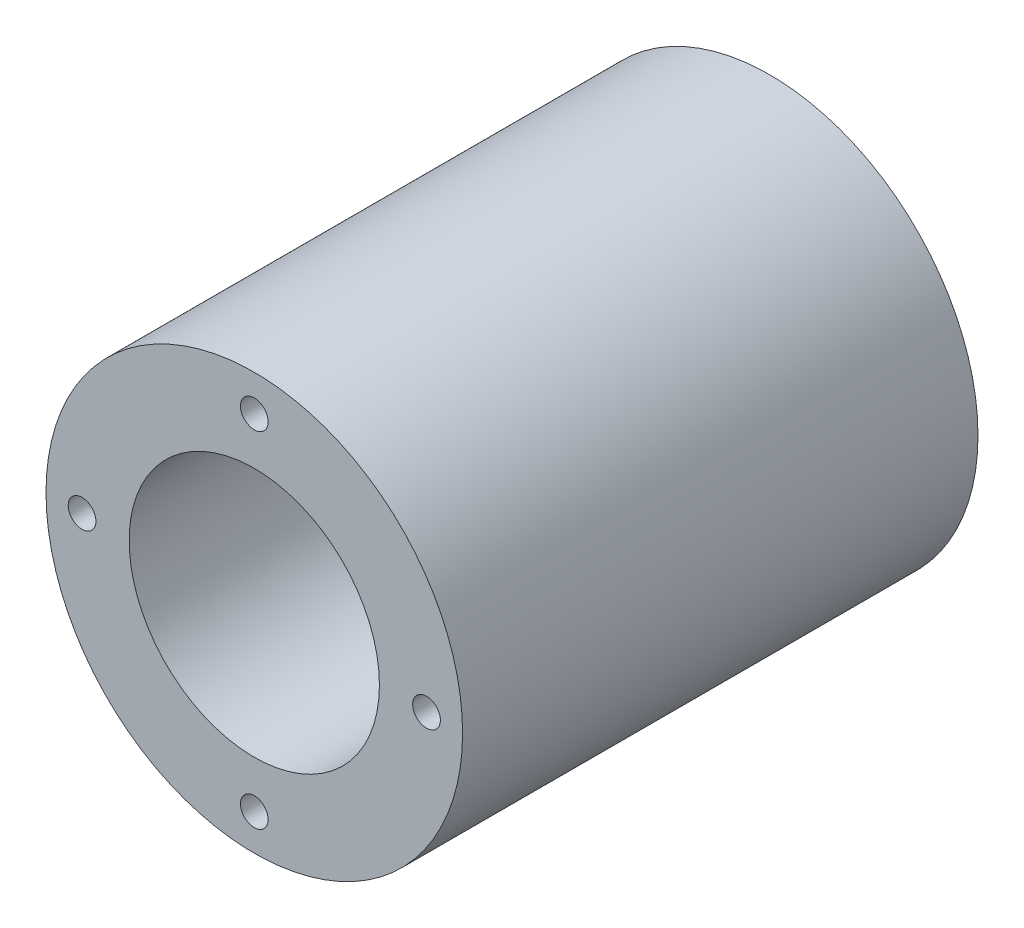
SolidWorks part; units mm, degrees
material "6061-T6 (SS)"
ref_plane "Front Plane" through (0, 0, 0) normal (0, 0, 1) x (1, 0, 0)
ref_plane "Top Plane" through (0, 0, 0) normal (0, 1, 0) x (1, 0, 0)
ref_plane "Right Plane" through (0, 0, 0) normal (1, 0, 0) x (0, 0, -1)
sketch "Sketch Spindle Skeleton" plane through (0, 0, 0) normal (1, 0, 0) x (0, 0, -1)
  line L0 (-95.847, -9.5) -> (-164, -9.5)
  line L5 (-1000, 0) -> (49000, 0)
  line L6 (0, -9.5) -> (0, 9.5)
  line L13 (0, 9.5) -> (-45.847, 9.5)
  line L26 (-45.847, 9.5) -> (-45.847, 14)
  line L27 (-45.847, 14) -> (-95.847, 14)
  line L32 (-95.847, 14) -> (-95.847, 9.5)
  line L34 (-180, 7) -> (-180, -7)
  line L36 (-95.847, -9.5) -> (-95.847, -14)
  line L37 (-95.847, -14) -> (-45.847, -14)
  line L38 (-45.847, -14) -> (-45.847, -9.5)
  line L39 (0, -9.5) -> (-45.847, -9.5)
  line L40 (-25.305, 37.6491) -> (-16.305, 37.6491)
  line L41 (-111.341, 22.6187) -> (-95.847, 22.6187)
  line L42 (-111.341, 22.6187) -> (-111.341, -22.6187)
  line L43 (-111.341, -22.6187) -> (-95.847, -22.6187)
  line L44 (-95.847, 22.6187) -> (-95.847, -22.6187)
  line L45 (-111.341, 22.6187) -> (-95.847, -22.6187) construction
  line L46 (-111.341, -22.6187) -> (-95.847, 22.6187) construction
  line L47 (-30.353, 22.6187) -> (-45.847, 22.6187)
  line L48 (-30.353, 22.6187) -> (-30.353, -22.6187)
  line L49 (-30.353, -22.6187) -> (-45.847, -22.6187)
  line L50 (-45.847, 22.6187) -> (-45.847, -22.6187)
  line L51 (-30.353, 22.6187) -> (-45.847, -22.6187) construction
  line L52 (-30.353, -22.6187) -> (-45.847, 22.6187) construction
  line L59 (-16.305, 37.6491) -> (-16.305, -37.6491)
  line L60 (-16.305, -37.6491) -> (-25.305, -37.6491)
  line L61 (-25.305, -22.6187) -> (-27.305, -22.6187)
  line L62 (-27.305, -22.6187) -> (-27.305, -12.5)
  line L63 (-27.305, -12.5) -> (-25.305, -12.5)
  line L64 (-25.305, -12.5) -> (-25.305, 12.5)
  line L65 (-25.305, 12.5) -> (-27.305, 12.5)
  line L66 (-27.305, 12.5) -> (-27.305, 22.6187)
  line L67 (-27.305, 22.6187) -> (-25.305, 22.6187)
  line L68 (-25.305, 22.6187) -> (-25.305, 37.6491)
  line L69 (-25.305, -22.6187) -> (-25.305, -37.6491)
  line L71 (-119.469, 37.6491) -> (-26.305, 37.6491)
  line L72 (-119.469, 37.6491) -> (-119.469, -37.6491)
  line L73 (-119.469, -37.6491) -> (-26.305, -37.6491)
  line L74 (-26.305, 37.6491) -> (-26.305, -37.6491)
  line L75 (-119.469, 37.6491) -> (-26.305, -37.6491) construction
  line L76 (-119.469, -37.6491) -> (-26.305, 37.6491) construction
  line L77 (-164, -9.5) -> (-164, -7)
  line L78 (-164, -7) -> (-180, -7)
  line L79 (-95.847, 9.5) -> (-164, 9.5)
  line L80 (-164, 7) -> (-180, 7)
  line L81 (-164, 9.5) -> (-164, 7)
  line L82 (-129.9235, 9.5) -> (-129.9235, -9.5) construction
  line L83 (-22.9235, 9.5) -> (-22.9235, -9.5) construction
  line L96 (-119.469, 37.6491) -> (-128.469, 37.6491)
  line L98 (-119.469, -37.6491) -> (-128.469, -37.6491)
  line L99 (-128.469, 37.6491) -> (-128.469, -37.6491)
  line L110 (-119.469, 37.6491) -> (-119.469, -37.6491)
  point P3 (0, 0)
  point P18 (-103.594, 0)
  point P24 (-38.1, 0)
  point P29 (-72.887, 0)
  point P48 (-16.305, 31.1339)
  point P70 (-128.469, 31.1339)
sketch "Sketch1" plane through (0, 0, 0) normal (1, 0, 0) x (0, 0, -1)
  line L0 (-26.305, 37.6491) -> (-26.305, -37.6491) construction
  line L1 (-119.469, -37.6491) -> (-26.305, -37.6491) construction
  line L2 (-119.469, 37.6491) -> (-119.469, -37.6491) construction
  line L3 (-119.469, 37.6491) -> (-26.305, 37.6491) construction
  line L4 (-26.305, 37.6491) -> (-26.305, -37.6491)
  line L5 (-119.469, -37.6491) -> (-26.305, -37.6491)
  line L6 (-119.469, 37.6491) -> (-119.469, -37.6491)
  line L7 (-119.469, 37.6491) -> (-26.305, 37.6491)
  line L9 (-30.353, 22.6187) -> (-45.847, 22.6187) construction
  line L10 (-119.469, 22.6187) -> (-26.305, 22.6187)
  line L15 (-119.469, 0) -> (-26.305, 0) construction
revolve "Revolve1" add sketch "Sketch1" angle 360 about L15 region at (0, 30.1339, 72.887)
sketch "Back Hole Top Location" plane through (0, 0, 26.305) normal (0, 0, -1) x (-1, 0, 0)
  point P9 (0, 31.1339)
hole_wizard "M6x1.0 Tapped Hole3" positions "Sketch8" profile "Sketch9" tap size "M6x1.0" standard "ANSI Metric"
sketch "Sketch8" plane through (0, 0, 26.305) normal (0, 0, -1) x (-1, 0, 0)
  point P0 (0, 31.1339)
sketch "Sketch9" plane through (0, 31.1339, 26.305) normal (1, 0, 0) x (0, 1, 0)
  line L0 (0, 0) -> (0, 16.5022)
  line L1 (0, 16.5022) -> (2.5, 15)
  line L2 (2.5, 15) -> (2.5, 0)
  line L5 (2.5, 0) -> (0, 0)
  line L10 (0, 16.5022) -> (-2.5, 15) construction
  line L11 (0, -6.35) -> (0, 107.95) construction
  dimension "Tap Drill Dia." = 5
  dimension "Tap Drill Depth" = 15
  dimension "Drill Angle" = 118
pattern_circular "BackFacePattern" count 6 over 360 about axis through (0, 0, 1000) along (0, 0, -1) of "M6x1.0 Tapped Hole3"
ref_plane "Midplane" through (0, 0, 72.887) normal (0, 0, -1) x (-1, 0, 0)
sketch "Front Hole Top Location" plane through (0, 0, 119.469) normal (0, 0, 1) x (1, 0, 0)
  point P0 (0, 31.1339)
hole_wizard "M6x1.0 Tapped Hole2" positions "Sketch5" profile "Sketch6" tap size "M6x1.0" standard "ANSI Metric"
sketch "Sketch5" plane through (0, 0, 119.469) normal (0, 0, 1) x (1, 0, 0)
  point P0 (0, 31.1339)
sketch "Sketch6" plane through (0, 31.1339, 119.469) normal (1, 0, 0) x (0, -1, 0)
  line L0 (0, 0) -> (0, 16.5022)
  line L1 (0, 16.5022) -> (2.5, 15)
  line L2 (2.5, 15) -> (2.5, 0)
  line L5 (2.5, 0) -> (0, 0)
  line L10 (0, 16.5022) -> (-2.5, 15) construction
  line L11 (0, -6.35) -> (0, 107.95) construction
  dimension "Tap Drill Dia." = 5
  dimension "Tap Drill Depth" = 15
  dimension "Drill Angle" = 118
pattern_circular "FrontFacePattern" count 4 over 360 about axis through (0, 0, 1000) along (0, 0, -1) of "M6x1.0 Tapped Hole2"
sketch "Sketch7" plane through (0, 0, 26.305) normal (0, 0, -1) x (-1, 0, 0)
  circle A0 centre (0, 0) radius 26.9875
  circle A1 centre (0, 0) radius 24.6062
  dimension "D1" = 53.975
  dimension "D2" = 49.2125
extrude "Cut-Extrude1" cut sketch "Sketch7" against normal blind 0.5
